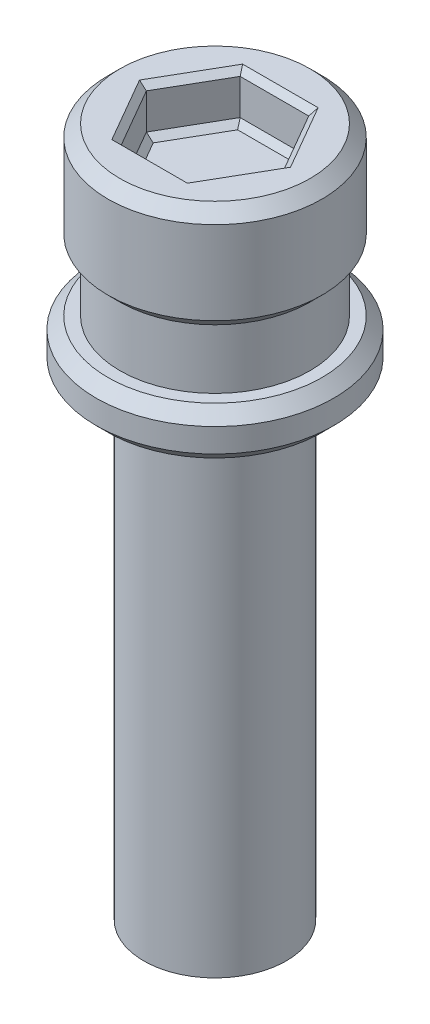
SolidWorks part; units mm, degrees
material "合金鋼"
ref_plane "正面" through (0, 0, 0) normal (0, 0, 1) x (1, 0, 0)
ref_plane "平面" through (0, 0, 0) normal (0, 1, 0) x (1, 0, 0)
ref_plane "右側面" through (0, 0, 0) normal (1, 0, 0) x (0, 0, -1)
sketch "ｽｹｯﾁ1" plane through (0, 0, 0) normal (0, 1, 0) x (1, 0, 0)
  circle A0 centre (0, 0) radius 4.5
extrude "ﾎﾞｽ - 押し出し1" add sketch "ｽｹｯﾁ1" along normal blind 4.5
sketch "ｽｹｯﾁ2" plane through (0, 4.5, 0) normal (0, 1, 0) x (1, 0, 0)
  line L1 (2.8868, 0) -> (1.4434, 2.5)
  line L2 (1.4434, 2.5) -> (-1.4434, 2.5)
  line L3 (-1.4434, 2.5) -> (-2.8868, 0)
  line L4 (-2.8868, 0) -> (-1.4434, -2.5)
  line L5 (-1.4434, -2.5) -> (1.4434, -2.5)
  line L6 (1.4434, -2.5) -> (2.8868, 0)
  circle A0 centre (0, 0) radius 2.5 construction
extrude "ｶｯﾄ - 押し出し1" cut sketch "ｽｹｯﾁ2" against normal blind 2
sketch "ｽｹｯﾁ3" plane through (0, 0, 0) normal (0, -1, 0) x (1, 0, 0)
  circle A0 centre (0, 0) radius 4
extrude "ﾎﾞｽ - 押し出し2" add sketch "ｽｹｯﾁ3" along normal blind 2.5
sketch "ｽｹｯﾁ4" plane through (0, -2.5, 0) normal (0, -1, 0) x (1, 0, 0)
  circle A0 centre (0, 0) radius 5
extrude "ﾎﾞｽ - 押し出し3" add sketch "ｽｹｯﾁ4" along normal blind 2
sketch "ｽｹｯﾁ5" plane through (0, -4.5, 0) normal (0, -1, 0) x (1, 0, 0)
  circle A0 centre (0, 0) radius 3
extrude "ﾎﾞｽ - 押し出し4" add sketch "ｽｹｯﾁ5" along normal blind 20
chamfer "面取り1" distance 0.5 angle 45 1 edges at (0, 4.5, 4.5)
chamfer "面取り2" distance 0.5 angle 45 1 edges at (0, 0, 4.5)
chamfer "面取り3" distance 0.5 angle 45 2 edges at (0, -4.5, -5) (0, -2.5, -5)
chamfer "面取り4" distance 0.25 angle 45 12 edges at (0, 4.5, 2.5) (-2.1651, 4.5, 1.25) (-2.1651, 4.5, -1.25) (0, 4.5, -2.5) (2.1651, 4.5, -1.25) (2.1651, 4.5, 1.25) (-2.1651, 2.5, -1.25) (-2.1651, 2.5, 1.25) (0, 2.5, -2.5) (2.1651, 2.5, -1.25) (2.1651, 2.5, 1.25) (0, 2.5, 2.5)
